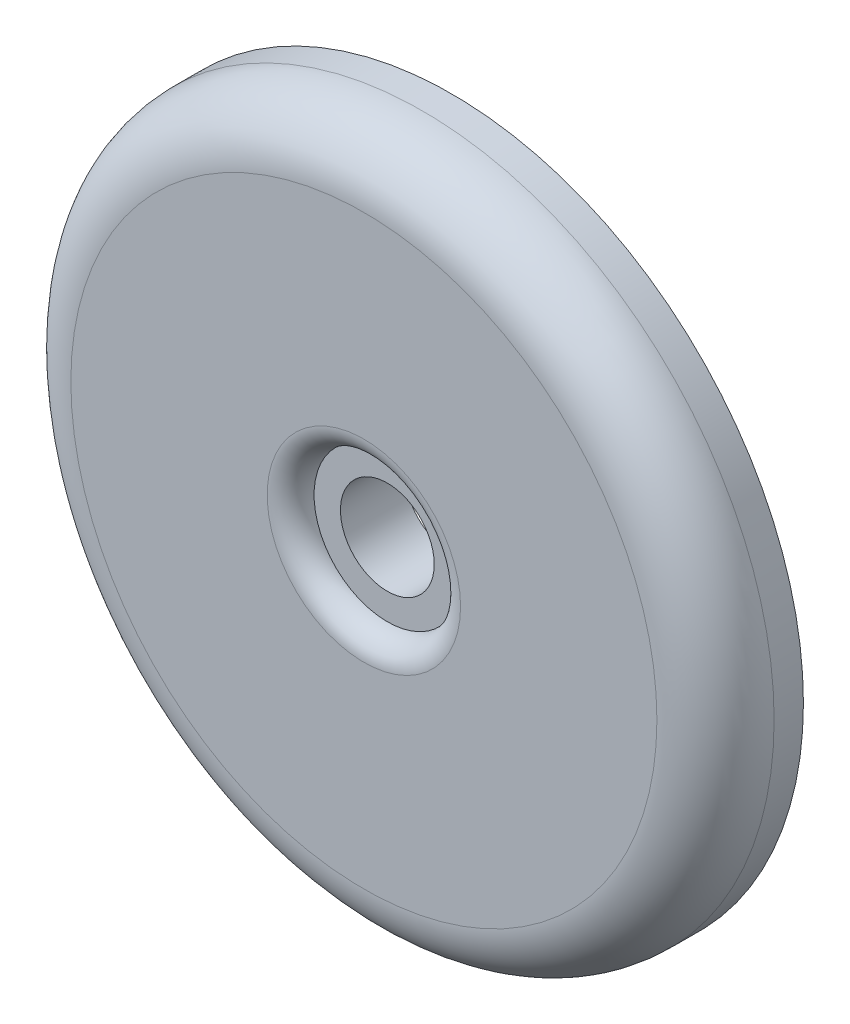
SolidWorks part; units mm, degrees
ref_plane "Спереди" through (0, 0, 0) normal (0, 0, 1) x (1, 0, 0)
ref_plane "Сверху" through (0, 0, 0) normal (0, 1, 0) x (1, 0, 0)
ref_plane "Справа" through (0, 0, 0) normal (1, 0, 0) x (0, 0, -1)
sketch "Эскиз1" plane through (0, 0, 0) normal (0, 0, 1) x (1, 0, 0)
  circle A0 centre (0, 0) radius 6
  circle A1 centre (0, 0) radius 0.8
  dimension "D1" = 12
  dimension "D2" = 1.6
extrude "Бобышка-Вытянуть1" add sketch "Эскиз1" along normal blind 1.5
fillet "Скругление1" radius 1 1 edges at (6, 0, 1.5)
sketch "Эскиз3" plane through (0, 0, 1.5) normal (0, 0, 1) x (1, 0, 0)
  circle A0 centre (0, 0) radius 1.25
  dimension "D1" = 2.5
extrude "Вырез-Вытянуть3" cut sketch "Эскиз3" against normal blind 0.4
fillet "Скругление2" radius 0.4 1 edges at (1.25, 0, 1.5)
